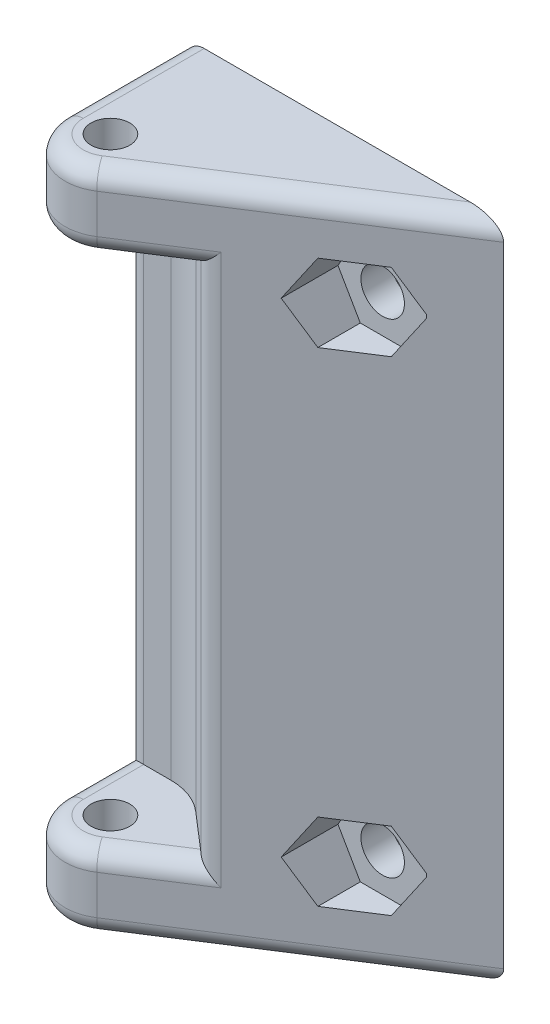
SolidWorks part; units mm, degrees
ref_plane "Front Plane" through (0, 0, 0) normal (0, 0, 1) x (1, 0, 0)
ref_plane "Top Plane" through (0, 0, 0) normal (0, 1, 0) x (1, 0, 0)
ref_plane "Right Plane" through (0, 0, 0) normal (1, 0, 0) x (0, 0, -1)
sketch "Sketch1" plane through (0, 0, 0) normal (0, 1, 0) x (1, 0, 0)
  line L2 (-4.7625, 12.7) -> (-4.7625, 0)
  line L3 (2.5745, -4.0067) -> (28.575, 12.7)
  line L4 (28.575, 12.7) -> (-4.7625, 12.7)
  circle A0 centre (0, 0) radius 2.032
  arc A1 (-4.7625, 0) -> (2.5745, -4.0067) centre (0, 0) ccw
  point P3 (28.2882, 12.7)
  point P5 (28.4934, 12.7)
  point P8 (28.4934, 12.7)
  dimension "D1" = 4.064
  dimension "D2" = 28.575
  dimension "D4" = 4.7625
  dimension "D5" = 12.7
extrude "Boss-Extrude1" add sketch "Sketch1" along normal mid plane 69.85
sketch "Sketch6" plane through (0, 0, 0) normal (0, 1, 0) x (1, 0, 0)
  line L0 (0, 6.35) -> (-4.7625, 6.35)
  line L1 (-4.7625, 12.7) -> (-4.7625, 0) construction
  line L2 (-4.7625, 6.35) -> (-4.7625, 0)
  line L3 (4.1512, 4.8052) -> (9.3281, 0.3329)
  line L4 (2.5745, -4.0067) -> (28.575, 12.7) construction
  line L5 (9.3281, 0.3329) -> (2.5745, -4.0067)
  arc A0 (-4.7625, 0) -> (2.5745, -4.0067) centre (0, 0) ccw
  arc A2 (4.1512, 4.8052) -> (0, 6.35) centre (0, 0) ccw
  dimension "D1" = 6.35
extrude "Cut-Extrude4" cut sketch "Sketch6" against normal mid plane 53.975
sketch "Sketch7" plane through (0, 0, -12.7) normal (0, 0, -1) x (-1, 0, 0)
  line L1 (-4.7347, 22.9788) -> (-6.8541, 18.792) construction
  line L2 (-6.8541, 18.792) -> (-4.2878, 14.8631) construction
  line L3 (-4.2878, 14.8631) -> (0.3978, 15.1212) construction
  line L4 (0.3978, 15.1212) -> (2.5171, 19.308) construction
  line L5 (2.5171, 19.308) -> (-0.0491, 23.2369) construction
  line L6 (-0.0491, 23.2369) -> (-4.7347, 22.9788) construction
  line L7 (-28.575, 34.925) -> (4.7625, 34.925) construction
  line L8 (4.7625, 19.05) -> (4.7625, 34.925)
  line L9 (-4.6644, 34.925) -> (4.7625, 34.925)
  line L11 (-8.8101, 21.0318) -> (-4.6644, 34.925)
  line L12 (0, 0) -> (-21.9875, 0) construction
  line L13 (4.7625, -19.05) -> (4.7625, -34.925)
  line L14 (-8.8101, -21.0318) -> (-4.6644, -34.925)
  line L15 (-4.6644, -34.925) -> (4.7625, -34.925)
  line L18 (-28.575, 34.925) -> (4.7625, 34.925) construction
  circle A0 centre (-2.1685, 19.05) radius 4.064 construction
  arc A1 (4.7625, 19.05) -> (-8.8101, 21.0318) centre (-2.1685, 19.05) ccw
  arc A2 (4.7625, -19.05) -> (-8.8101, -21.0318) centre (-2.1685, -19.05) cw
  dimension "D2" = 38.1
  dimension "D1" = 8.128
extrude "Boss-Extrude2" add sketch "Sketch7" against normal blind 6.35
sketch "Sketch13" plane through (0, 0, -12.7) normal (0, 0, -1) x (-1, 0, 0)
  line L0 (-19.05, 25.4) -> (-19.05, -25.4) construction
  circle A0 centre (-19.05, 25.4) radius 2.286
  circle A1 centre (-19.05, -25.4) radius 2.286
  point P4 (-19.05, 0)
  dimension "D1" = 4.572
  dimension "D2" = 50.8
  dimension "D3" = 19.05
extrude "Cut-Extrude9" cut sketch "Sketch13" against normal through all
sketch "Sketch14" plane through (0, 0, -12.7) normal (0, 0, -1) x (-1, 0, 0)
  line L1 (-14.3573, 25.4) -> (-16.7036, 29.464)
  line L2 (-16.7036, 29.464) -> (-21.3964, 29.464)
  line L3 (-21.3964, 29.464) -> (-23.7427, 25.4)
  line L4 (-23.7427, 25.4) -> (-21.3964, 21.336)
  line L5 (-21.3964, 21.336) -> (-16.7036, 21.336)
  line L6 (-16.7036, 21.336) -> (-14.3573, 25.4)
  line L7 (-14.3573, -25.4) -> (-16.7036, -21.336)
  line L8 (-16.7036, -21.336) -> (-21.3964, -21.336)
  line L9 (-21.3964, -21.336) -> (-23.7427, -25.4)
  line L10 (-23.7427, -25.4) -> (-21.3964, -29.464)
  line L11 (-21.3964, -29.464) -> (-16.7036, -29.464)
  line L12 (-16.7036, -29.464) -> (-14.3573, -25.4)
  circle A0 centre (-19.05, 25.4) radius 4.064 construction
  circle A1 centre (-19.05, -25.4) radius 4.064 construction
  dimension "D1" = 8.128
  dimension "D2" = 8.128
extrude "Cut-Extrude10" cut sketch "Sketch14" against normal through all from offset 3.175 offset against normal yes
fillet "Fillet1" radius 1.905 14 edges at (-4.7625, -34.925, -6.35) (-2.2826, -34.925, 4.1799) (15.5747, 34.925, -4.3467) (-2.2826, 34.925, 4.1799) (15.5747, -34.925, -4.3467) (-4.7625, 34.925, -6.35) (-4.7625, -26.9875, -3.175) (5.9513, -26.9875, 1.8369) (-4.7625, 26.9875, -3.175) (-2.2826, 26.9875, 4.1799) (-2.2826, -26.9875, 4.1799) (5.9513, 26.9875, 1.8369) (-4.7625, 0, -6.35) (9.3281, 0, -0.3329)
